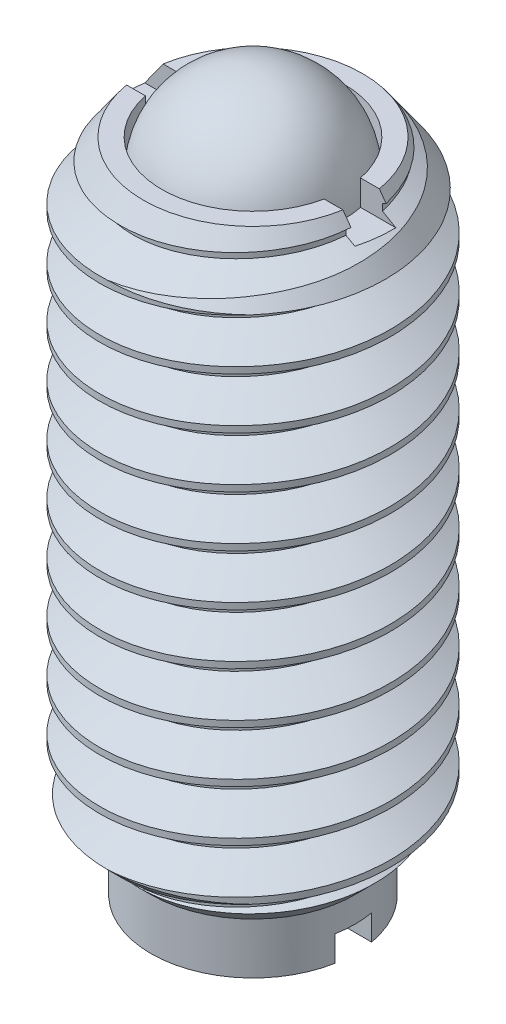
SolidWorks part; units mm, degrees
ref_plane "Front" through (0, 0, 0) normal (0, 0, 1) x (1, 0, 0)
ref_plane "Top" through (0, 0, 0) normal (0, 1, 0) x (1, 0, 0)
ref_plane "Right" through (0, 0, 0) normal (1, 0, 0) x (0, 0, -1)
sketch "Sketch24" plane through (0, 0, 0) normal (1, 0, 0) x (0, 0, -1)
  line L0 (2, 4.5) -> (-2, 4.5) construction
  line L1 (0, 4.5) -> (2, 4.5)
  line L2 (0, 4.5) -> (0, -4.5)
  line L3 (0, -4.5) -> (2, -4.5)
  line L4 (2, 4.5) -> (2, -4.5)
  point P5 (2, 1.35)
  dimension "Body Length" = 9
  dimension "Screw Dia" = 4
  dimension "D1" = 3.15
revolve "Revolve1" add sketch "Sketch24" angle 360 about L2
sketch "Sketch37" plane through (0, 4.5, 0) normal (0, 1, 0) x (1, 0, 0)
  circle A1 centre (0, 0) radius 2
  circle A2 centre (0, 0) radius 2
  dimension "D1" = 0
curve "Helix/Spiral1" pitch 0.7 height 9.7 turns 13.8571 parameters "pitch"=0.7
sketch "Sketch38" plane through (0, 0, 0) normal (1, 0, 0) x (0, 0, -1)
  line L0 (-2, 5.1125) -> (-2, 4.5)
  line L1 (-2, 5.1125) -> (-1.5453, 4.85)
  line L2 (-1.5453, 4.85) -> (-1.5453, 4.7625)
  line L3 (-1.5453, 4.7625) -> (-2, 4.5)
  line L4 (-1.5453, 4.8062) -> (-2, 4.8062) construction
  line L5 (-1.7727, 4.9812) -> (-1.7727, 4.6312) construction
  line L6 (2, 4.5) -> (-2, 4.5) construction
  line L7 (0, 0) -> (0, 4.5) construction
  dimension "D1" = 0.0875
  dimension "D2" = 0.35
  dimension "D3" = 60
  dimension "D4" = 0.4547
  dimension "D5" = 1.5453
  dimension "D6" = 0.2273
sweep "Cut-Sweep1" cut profiles "Sketch38" path "Helix/Spiral1" align with end faces yes
sketch "Sketch26" plane through (0, 0, 0) normal (1, 0, 0) x (0, 0, -1)
  line L0 (0, -3.6) -> (0, 4.5)
  line L1 (0, 4.5) -> (0, -4.5) construction
  line L2 (0, 4.5) -> (1.25, 4.5)
  line L3 (1.25, 4.5) -> (1.25, -3.6)
  line L5 (1.25, -3.6) -> (0, -3.6)
  line L7 (1.25, 4.5) -> (-1.25, 4.5) construction
  line L8 (2, 4.5) -> (-2, 4.5) construction
  dimension "D1" = 0.9
  dimension "Ball Dia" = 2.5
revolve "Cut-Revolve10" cut sketch "Sketch26" angle 360 about L0
sketch "Sketch31" plane through (0, 0, 0) normal (1, 0, 0) x (0, 0, -1)
  line L0 (2, -4.5) -> (1.4, -4.5)
  line L1 (2, 4.5) -> (2, -4.5) construction
  line L2 (1.4, -4.5) -> (1.4, -3.8)
  line L3 (0, 0) -> (0, -14.5366) construction
  line L4 (1.4, -3.8) -> (2, -3.2)
  line L5 (0, 0) -> (2, 0) construction
  line L14 (2, 4.5) -> (1.504, 4.5)
  line L15 (0, 4.5) -> (2, 4.5) construction
  line L16 (1.504, 4.5) -> (2, 3.8)
  line L17 (2, 3.8) -> (2, 4.5)
  line L18 (2, -3.2) -> (2, -4.5)
  dimension "D1" = 0.254
  dimension "D2" = 45
  dimension "D3" = 0.7
  dimension "D4" = 1.4
revolve "Cut-Revolve13" cut sketch "Sketch31" angle 360 about L2
sketch "Sketch28" plane through (0, 0, 0) normal (1, 0, 0) x (0, 0, -1)
  line L0 (1.4, -4.15) -> (0.25, -4.15) construction
  line L1 (-0.25, -4.5) -> (0.25, -4.5)
  line L2 (-0.25, -4.5) -> (-0.25, -4.15)
  line L3 (-0.25, -4.15) -> (0.25, -4.15)
  line L4 (0.25, -4.5) -> (0.25, -4.15)
  line L5 (2, 4.5) -> (-2, 4.5) construction
  line L6 (-0.25, 4.5) -> (0.25, 4.5)
  line L7 (-0.25, 4.5) -> (-0.25, 4.15)
  line L8 (-0.25, 4.15) -> (0.25, 4.15)
  line L9 (0.25, 4.5) -> (0.25, 4.15)
  line L10 (1.4, -4.5) -> (1.4, -3.8) construction
  dimension "D1" = 0.5
extrude "Cut-Extrude11" cut sketch "Sketch28" against normal through all and the other way through all
sketch "Sketch27" plane through (0, 0, 0) normal (1, 0, 0) x (0, 0, -1)
  line L0 (0, 4.5) -> (0, -4.5) construction
  line L1 (1.25, 4.5) -> (1.25, -3.6) construction
  line L2 (0, -4.5) -> (0, 2.8) construction
  line L3 (0, 5.3) -> (0, 2.8)
  circle A0 centre (0, 4.05) radius 1.25 construction
  arc A1 (0, 5.3) -> (0, 2.8) centre (0, 4.05) cw
  dimension "Ball Projection" = 0.8
revolve "Revolve2" add sketch "Sketch27" angle 360 about L3
ref_plane "Plane1" [suppressed] through (-3, 0, 0) normal (1, 0, 0) x (0, 0, -1)
sketch "Sketch21" [suppressed] plane through (-3, 0, 0) normal (1, 0, 0) x (0, 0, -1)
  line L0 (0, -1.7183) -> (0, -3.2804) construction
  line L2 (3, 7) -> (-3, 7) construction
  line L3 (0, 7) -> (0, -7) construction
  ellipse E0 centre (0, 1.4285) end of major axis (0, 3.3785) minor radius 1.5
  dimension "D5" = 2
  dimension "D6" = 2.6
  dimension "D7" = 2.5351
sketch "Sketch41" [suppressed] plane through (-3, 0, 0) normal (1, 0, 0) x (0, 0, -1)
  ellipse E1 centre (0, 1.4285) end of major axis (0, 3.3785) minor radius 1.5
  ellipse E2 centre (0, 1.4285) end of major axis (0, 3.3785) minor radius 1.5
  dimension "D1" = 0
sketch "Sketch43" [suppressed] plane through (0, 0, 0) normal (1, 0, 0) x (0, 0, -1)
  ellipse E1 centre (0, 1.4285) end of major axis (0, 3.3785) minor radius 1.5
  ellipse E2 centre (0, 1.4285) end of major axis (0, 3.3785) minor radius 1.5
  dimension "D1" = 0
extrude "Extrude9" [suppressed] cut sketch "Sketch43" against normal through all
sketch "Sketch44" [suppressed] plane through (0, 0, 0) normal (1, 0, 0) x (0, 0, -1)
  ellipse E1 centre (0, 1.4285) end of major axis (0, 3.3785) minor radius 1.5
  ellipse E2 centre (0, 1.4285) end of major axis (0, 3.3785) minor radius 1.5
  dimension "D1" = 0
extrude "Extrude10" [suppressed] add sketch "Sketch44" against normal blind 1.5453 separate body
dome "Dome1" [suppressed] faces to dome 1 distance 0.2273 parameters "D1"=0.2273
sketch "Sketch45" plane through (0, 0, 0) normal (0, 1, 0) x (1, 0, 0)
  circle A0 centre (0, 0) radius 1.25
  arc A1 (-1.2247, -0.25) -> (1.2247, -0.25) centre (0, 0) ccw construction
extrude "Extrude11" [suppressed] cut sketch "Sketch45" against normal through all and the other way through all
equation "\"D1@Sketch26\" = \"Body Length@Sketch24\"*.1"
equation "\"D1@Sketch28\" = \"Screw Dia@Sketch24\"/8"
equation "\"D1@Sketch38\" = \"pitch@Helix/Spiral1\"*.125"
equation "\"D2@Sketch38\" = \"pitch@Helix/Spiral1\"*.50"
equation "\"D3@Helix/Spiral1\" = \"Body Length@Sketch24\"+\"pitch@Helix/Spiral1\""
equation "\"D3@Sketch31\" = \"pitch@Helix/Spiral1\""
equation "\"D4@Sketch31\" = (\"Screw Dia@Sketch24\"/2)*.7"
equation "\"D5@Sketch21\" = \"Screw Dia@Sketch24\"*.50"
equation "\"D6@Sketch21\" = \"D5@Sketch21\"*1.3"
equation "\"D7@Sketch21\" = \"pitch@Helix/Spiral1\"*3.62154"
equation "\"D1@Sketch24\" = \"pitch@Helix/Spiral1\"*4.50"
equation "\"D1@Plane1\" = \"Screw Dia@Sketch24\"/2"
equation "\"D1@Extrude10\" = \"D5@Sketch38\""
equation "\"D1@Dome1\" = \"D6@Sketch38\""
